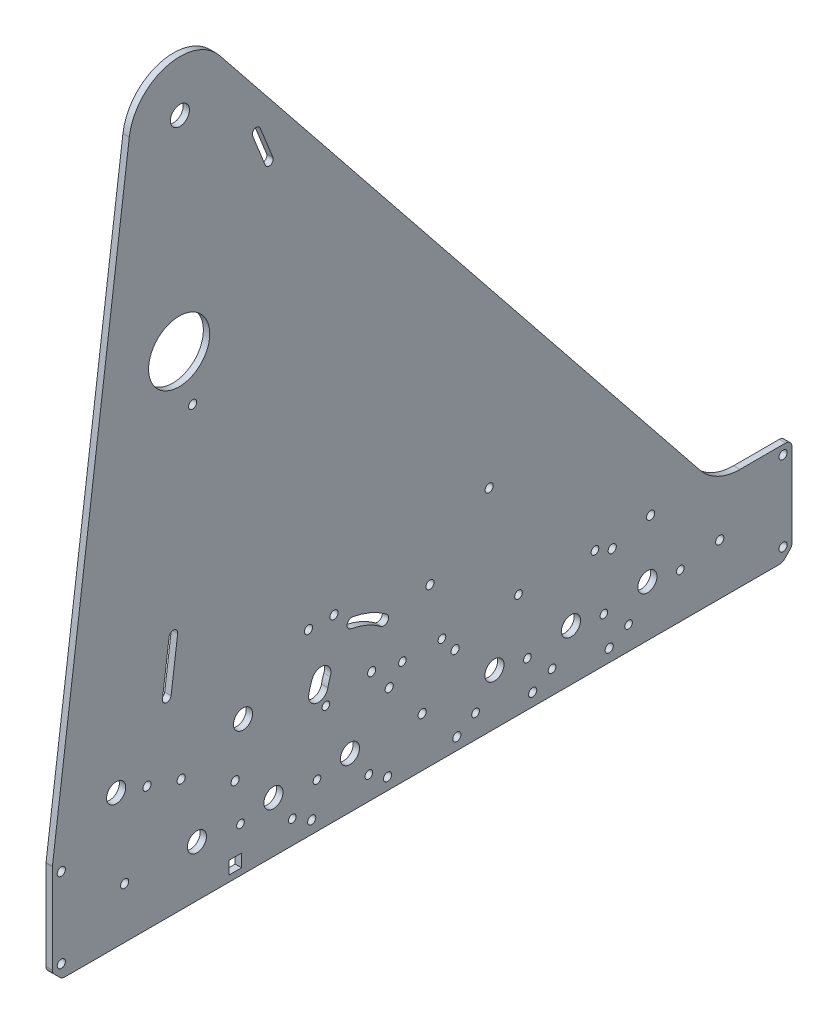
SolidWorks part; units mm, degrees
ref_plane "Front Plane" through (0, 0, 0) normal (0, 0, 1) x (1, 0, 0)
ref_plane "Top Plane" through (0, 0, 0) normal (0, 1, 0) x (1, 0, 0)
ref_plane "Right Plane" through (0, 0, 0) normal (1, 0, 0) x (0, 0, -1)
sketch "Sketch1" plane through (0, 0, 0) normal (1, 0, 0) x (0, 0, -1)
  line L0 (-184.15, -24.6062) -> (184.15, -24.6062)
  line L1 (184.15, -24.6062) -> (184.15, 26.1938)
  line L2 (184.15, 26.1938) -> (146.05, 26.1937)
  line L5 (-145.839, 321.5609) -> (-184.15, 26.1938)
  line L6 (-184.15, 26.1938) -> (-184.15, -24.6062)
  line L7 (-184.15, 350.0437) -> (184.15, 350.0437) construction
  line L9 (146.05, 26.1937) -> (-100.8314, 334.1803)
  arc A0 (-100.8314, 334.1803) -> (-145.839, 321.5609) centre (-120.65, 318.2937) ccw
  point P8 (0, -24.6062)
  dimension "D1" = 368.3
  dimension "D7" = 25.4
  dimension "D2" = 50.8
  dimension "D3" = 38.1
  dimension "D4" = 24.6062
  dimension "D5" = 374.65
  dimension "D6" = 304.8
  dimension "D8" = 342.9
extrude "Boss-Extrude1" add sketch "Sketch1" along normal blind 3.175
chamfer "Chamfer1" distance 4.7625 angle 45 2 edges at (1.5875, -24.6062, 184.15) (1.5875, -24.6062, -184.15)
fillet "Fillet1" radius 25.4 1 edges at (1.5875, 26.1937, -146.05)
fillet "Fillet2" radius 3.175 2 edges at (1.5875, 26.1938, 184.15) (1.5875, 26.1938, -184.15)
fillet "Fillet3" radius 3.175 4 edges at (1.5875, -19.8438, -184.15) (1.5875, -24.6062, -179.3875) (1.5875, -19.8437, 184.15) (1.5875, -24.6062, 179.3875)
sketch "Sketch30" plane through (3.175, 0, 0) normal (1, 0, 0) x (0, 0, -1)
  circle A8 centre (-89.211, 42.2593) radius 4.7625
  circle A9 centre (-25.1593, 30.6938) radius 2.032
  arc A10 (-51.7173, 35.4892) -> (-50.2741, 40.5715) centre (-25.1593, 30.6938) cw construction
  arc A11 (-54.7652, 42.3379) -> (-56.4665, 36.3468) centre (-25.1593, 30.6938) ccw
  arc A12 (-45.783, 38.8051) -> (-46.9681, 34.6317) centre (-25.1593, 30.6938) ccw
  arc A13 (-45.783, 38.8051) -> (-54.7652, 42.3379) centre (-50.2741, 40.5715) ccw
  arc A14 (-56.4665, 36.3468) -> (-46.9681, 34.6317) centre (-51.7173, 35.4892) ccw
  arc A15 (-34.9881, 56.6661) -> (-19.1131, 49.8125) centre (-41.7582, 19.1724) cw construction
  arc A16 (-17.6789, 51.753) -> (-34.5594, 59.0407) centre (-41.7582, 19.1724) ccw
  arc A17 (-20.5473, 47.8719) -> (-35.4169, 54.2915) centre (-41.7582, 19.1724) ccw
  arc A18 (-20.5473, 47.8719) -> (-17.6789, 51.753) centre (-19.1131, 49.8125) ccw
  arc A19 (-34.5594, 59.0407) -> (-35.4169, 54.2915) centre (-34.9881, 56.6661) ccw
  arc A20 (-19.1131, 49.8125) -> (-34.9881, 56.6661) centre (-41.7582, 19.1724) ccw construction
  circle A21 centre (94.6345, 23.8125) radius 2.032
  circle A22 centre (-56.6241, 64.5541) radius 2.032
  circle A23 centre (-43.9241, 64.5541) radius 2.032
  circle A24 centre (-56.6241, 64.5541) radius 1.905 construction
  circle A25 centre (-43.9241, 64.5541) radius 1.905 construction
  point P7 (-51.1204, 38.0658)
  point P19 (-26.6567, 54.1518)
  dimension "D2" = 9.652
  dimension "D4" = 4.064
  dimension "D1" = 4.064
  dimension ".375" = 9.525
  dimension "D3" = 4.826
extrude "Cut-Extrude9" cut sketch "Sketch30" against normal through all
sketch "Sketch16" plane through (3.175, 0, 0) normal (1, 0, 0) x (0, 0, -1)
  circle A0 centre (112.1746, 0.7937) radius 4.7625
  circle A1 centre (74.0746, 0.7937) radius 4.7625
  circle A2 centre (35.9746, 0.7937) radius 4.7625
  circle A3 centre (-35.9746, 0.7938) radius 4.7625
  circle A4 centre (-74.0746, 0.7938) radius 4.7625
  circle A5 centre (-112.1746, 0.7937) radius 4.7625
  dimension "D1" = 9.525
  dimension "D2" = 9.525
extrude "Cut-Extrude1" cut sketch "Sketch16" against normal up to next
sketch "Sketch25" plane through (3.175, 0, 0) normal (1, 0, 0) x (0, 0, -1)
  circle A0 centre (102.7672, -13.0003) radius 1.905 construction
  circle A1 centre (86.0486, 27.3622) radius 1.905 construction
  circle A2 centre (128.5804, -2.3081) radius 1.905 construction
  circle A3 centre (102.7672, -13.0003) radius 1.905
  circle A4 centre (86.0486, 27.3622) radius 1.905
  circle A5 centre (128.5804, -2.3081) radius 1.905
  circle A6 centre (64.6672, -13.0003) radius 1.905 construction
  circle A8 centre (-9.8486, 27.3622) radius 1.905 construction
  circle A10 centre (-47.9486, 27.3622) radius 1.905 construction
  circle A11 centre (-90.4804, -2.3081) radius 1.905 construction
  circle A12 centre (-64.6672, -13.0003) radius 1.905 construction
  circle A14 centre (-52.3804, -2.3081) radius 1.905 construction
  circle A15 centre (-26.5672, -13.0003) radius 1.905 construction
  circle A16 centre (9.8486, 27.3622) radius 1.905 construction
  circle A17 centre (26.5672, -13.0003) radius 1.905 construction
  circle A18 centre (47.9486, 27.3622) radius 1.905 construction
  circle A19 centre (52.3804, -2.3081) radius 1.905 construction
  circle A20 centre (90.4804, -2.3081) radius 1.905 construction
  circle A21 centre (-9.8486, 27.3622) radius 1.905
  circle A23 centre (-47.9486, 27.3622) radius 1.905
  circle A24 centre (-90.4804, -2.3081) radius 1.905
  circle A25 centre (-64.6672, -13.0003) radius 1.905
  circle A27 centre (-52.3804, -2.3081) radius 1.905
  circle A28 centre (-26.5672, -13.0003) radius 1.905
  circle A29 centre (9.8486, 27.3622) radius 1.905
  circle A30 centre (26.5672, -13.0003) radius 1.905
  circle A31 centre (47.9486, 27.3622) radius 1.905
  circle A32 centre (64.6672, -13.0003) radius 1.905
  circle A33 centre (52.3804, -2.3081) radius 1.905
  circle A34 centre (90.4804, -2.3081) radius 1.905
extrude "Cut-Extrude4" cut sketch "Sketch25" against normal up to next
sketch "Sketch23" plane through (3.175, 0, 0) normal (1, 0, 0) x (0, 0, -1)
  circle A0 centre (179.705, 21.7488) radius 1.905 construction
  point P0 (-55.0246, -18.3223)
  point P6 (-93.1246, 17.5943)
  point P9 (-17.2515, -18.6426)
  point P12 (-16.4124, 19.3854)
  point P15 (16.4124, 19.3854)
  point P18 (17.2515, -18.6426)
  point P21 (55.0246, -18.3223)
  point P35 (3.8736, 53.6853)
  point P38 (113.7728, 28.6594)
  point P41 (-137.0088, 37.226)
  point P44 (-179.705, 21.7487)
  point P47 (-179.705, -18.0026)
  point P50 (179.705, 21.7488)
  point P53 (179.705, -18.0026)
  point P59 (93.1246, -18.3223)
hole_wizard "#8 (0.16) Diameter Hole1" positions "Sketch23" profile "Sketch24" hole size "#8" standard "ANSI Inch" end condition up to next
sketch "Sketch24" plane through (3.175, -18.3223, 55.0246) normal (0, 1, 0) x (0, 0, -1)
  line L0 (0, 0) -> (0, 3.175)
  line L1 (0, 3.175) -> (2.032, 3.175)
  line L2 (2.032, 3.175) -> (2.032, 0)
  line L5 (2.032, 0) -> (0, 0)
  line L11 (0, -6.35) -> (0, 107.95) construction
  dimension "Thru Hole Dia." = 4.064
  dimension "Thru Hole Depth" = 3.175
sketch "Sketch22" plane through (3.175, 0, 0) normal (1, 0, 0) x (0, 0, -1)
  line L0 (-96.2996, -15.1473) -> (-89.9496, -15.1473) construction
  line L1 (-96.2996, -15.1473) -> (-89.9496, -15.1473)
  line L2 (-96.2996, -15.1473) -> (-96.2996, -21.4973)
  line L3 (-96.2996, -21.4973) -> (-89.9496, -21.4973)
  line L4 (-89.9496, -15.1473) -> (-89.9496, -21.4973)
  line L5 (-96.2996, -15.1473) -> (-89.9496, -21.4973) construction
  line L6 (-96.2996, -21.4973) -> (-89.9496, -15.1473) construction
  line L7 (-89.9496, -15.1473) -> (-89.9496, -19.8734) construction
  point P0 (-93.1246, -18.3223)
  dimension "D1" = 6.35
extrude "Cut-Extrude3" cut sketch "Sketch22" against normal up to next
sketch "Sketch21" plane through (3.175, 0, 0) normal (1, 0, 0) x (0, 0, -1)
  circle A0 centre (-148.1579, 0.7937) radius 2.032
  circle A2 centre (0, 0) radius 2.032
  circle A3 centre (148.1579, 0.7938) radius 2.032
  dimension "D1" = 4.064
extrude "Cut-Extrude2" cut sketch "Sketch21" against normal up to next
sketch "Sketch26" plane through (3.175, 0, 0) normal (1, 0, 0) x (0, 0, -1)
  line L0 (-145.839, 321.5609) -> (-184.1236, 26.3971) construction
  line L1 (-178.0724, -24.6062) -> (178.0724, -24.6062) construction
  circle A0 centre (-121.0218, 216.6937) radius 15.24
  dimension "D1" = 30.48
  dimension "D2" = 38.1
  dimension "D3" = 241.3
extrude "Cut-Extrude5" cut sketch "Sketch26" against normal through all
sketch "Sketch27" plane through (3.175, 0, 0) normal (1, 0, 0) x (0, 0, -1)
  circle A0 centre (-120.65, 318.2937) radius 4.7625
  dimension "D1" = 9.525
extrude "Cut-Extrude6" cut sketch "Sketch27" against normal through all
sketch "Sketch28" plane through (3.175, 0, 0) normal (1, 0, 0) x (0, 0, -1)
  line L0 (-120.65, 318.2937) -> (-103.5612, 277.2599) construction
  line L1 (-103.5612, 277.2599) -> (-86.3654, 258.566) construction
  line L2 (-86.3654, 258.566) -> (-90.1612, 246.4465) construction
  line L3 (-90.1612, 246.4465) -> (-93.9569, 234.327) construction
  line L4 (-145.839, 321.5609) -> (-184.1236, 26.3971) construction
  circle A0 centre (-93.9569, 234.327) radius 2.032
  circle A1 centre (-90.1612, 246.4465) radius 2.032
  circle A2 centre (-86.3654, 258.566) radius 2.0955
  circle A3 centre (-103.5612, 277.2599) radius 2.032
  dimension "D4" = 4.064
  dimension "D5" = 4.191
  dimension "D6" = 4.064
  dimension "D1" = 25.4
  dimension "D2" = 44.45
  dimension "D3" = 12.7
  dimension "D7" = 30
  dimension "D8" = 120
  dimension "D9" = 160
extrude "Cut-Extrude7" [suppressed] cut sketch "Sketch28" against normal through all
sketch "Sketch29" plane through (3.175, 0, 0) normal (1, 0, 0) x (0, 0, -1)
  line L1 (-82.55, 292.1) -> (-76.2, 276.225) construction
  line L2 (-80.6633, 292.8547) -> (-74.3133, 276.9797)
  line L3 (-84.4367, 291.3453) -> (-78.0867, 275.4703)
  arc A4 (-80.6633, 292.8547) -> (-84.4367, 291.3453) centre (-82.55, 292.1) ccw
  arc A5 (-78.0867, 275.4703) -> (-74.3133, 276.9797) centre (-76.2, 276.225) ccw
  point P8 (-79.375, 284.1625)
  dimension "D1" = 276.225
  dimension "D2" = 2.032
  dimension "D3" = 76.2
  dimension "D4" = 82.55
  dimension "D5" = 292.1
sketch "Sketch31" plane through (0, 0, 0) normal (-1, 0, 0) x (0, 0, 1)
  circle A1 centre (114.3, 190.5) radius 2.032
  dimension "D1" = 114.3
  dimension "D6" = 4.064
  dimension "D2" = 190.5
extrude "Cut-Extrude10" cut sketch "Sketch31" against normal through all
sketch "Sketch34" plane through (0, 0, 0) normal (-1, 0, 0) x (0, 0, 1)
  line L3 (123.9045, 95.7355) -> (127.1716, 70.5465) construction
  line L4 (126.0455, 96.0132) -> (129.3127, 70.8242)
  line L5 (121.7634, 95.4578) -> (125.0306, 70.2688)
  line L6 (145.839, 321.5609) -> (184.1236, 26.3971) construction
  arc A2 (126.0455, 96.0132) -> (121.7634, 95.4578) centre (123.9045, 95.7355) ccw
  arc A3 (125.0306, 70.2688) -> (129.3127, 70.8242) centre (127.1716, 70.5465) ccw
  point P9 (125.538, 83.141)
  point P18 (114.3, 190.5)
  dimension "D8" = 4.318
  dimension "D6" = 50.8
  dimension "D7" = 25.4
  dimension "D9" = 95.25
extrude "Cut-Extrude12" cut sketch "Sketch34" against normal through all
sketch "Sketch37" plane through (3.175, 0, 0) normal (1, 0, 0) x (0, 0, -1)
  circle A0 centre (33.3375, 80.645) radius 2.032
  circle A8 centre (0, 0) radius 2.032 construction
  dimension "D1" = 4.064
  dimension "D2" = 33.3375
  dimension "D3" = 80.645
extrude "Cut-Extrude13" cut sketch "Sketch37" against normal through all
sketch "Sketch38" plane through (3.175, 0, 0) normal (1, 0, 0) x (0, 0, -1)
  line L0 (-184.15, 25.9887) -> (-184.15, -18.5286) construction
  line L1 (-178.0724, -24.6062) -> (178.0724, -24.6062) construction
  circle A0 centre (-152.4, 42.0688) radius 4.7625
  dimension "D1" = 31.75
  dimension "D3" = 9.525
  dimension "D2" = 66.675
extrude "Cut-Extrude14" cut sketch "Sketch38" against normal through all
extrude "Cut-Extrude15" cut sketch "Sketch29" against normal through all
sketch "Sketch40" plane through (3.175, 0, 0) normal (1, 0, 0) x (0, 0, -1)
  circle A0 centre (-120.015, 31.75) radius 2.032
  dimension "D1" = 4.064
  dimension "D2" = 120.015
  dimension "D3" = 31.75
extrude "Cut-Extrude16" cut sketch "Sketch40" against normal through all
